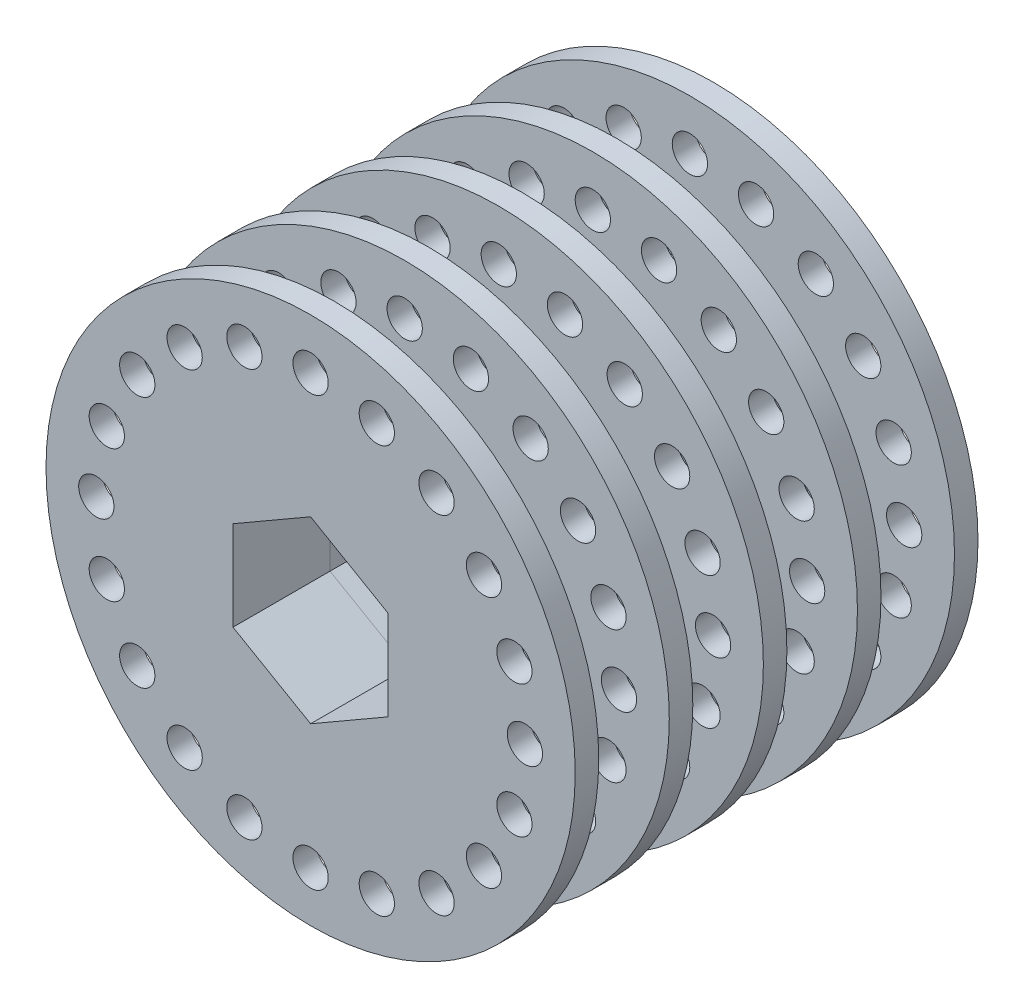
SolidWorks part; units mm, degrees
ref_plane "Front Plane" through (0, 0, 0) normal (0, 0, 1) x (1, 0, 0)
ref_plane "Top Plane" through (0, 0, 0) normal (0, 1, 0) x (1, 0, 0)
ref_plane "Right Plane" through (0, 0, 0) normal (1, 0, 0) x (0, 0, -1)
sketch "Sketch1" plane through (0, 0, 0) normal (0, 0, 1) x (1, 0, 0)
  circle A0 centre (0, 0) radius 10.16
  circle A1 centre (0, 0) radius 22.5
  circle A2 centre (0, 18.2218) radius 1.5
  circle A3 centre (5.6309, 17.33) radius 1.5
  circle A4 centre (10.7105, 14.7418) radius 1.5
  circle A5 centre (14.7418, 10.7105) radius 1.5
  circle A6 centre (17.33, 5.6309) radius 1.5
  circle A7 centre (18.2218, 0) radius 1.5
  circle A8 centre (17.33, -5.6309) radius 1.5
  circle A9 centre (14.7418, -10.7105) radius 1.5
  circle A10 centre (10.7105, -14.7418) radius 1.5
  circle A11 centre (5.6309, -17.33) radius 1.5
  circle A12 centre (0, -18.2218) radius 1.5
  circle A13 centre (-5.6309, -17.33) radius 1.5
  circle A14 centre (-10.7105, -14.7418) radius 1.5
  circle A15 centre (-14.7418, -10.7105) radius 1.5
  circle A16 centre (-17.33, -5.6309) radius 1.5
  circle A17 centre (-18.2218, 0) radius 1.5
  circle A18 centre (-17.33, 5.6309) radius 1.5
  circle A19 centre (-14.7418, 10.7105) radius 1.5
  circle A20 centre (-10.7105, 14.7418) radius 1.5
  circle A21 centre (-5.6309, 17.33) radius 1.5
  point P47 (0, 0)
  dimension "D1" = 20.32
  dimension "D2" = 45
  dimension "D3" = 3
  dimension "D4" = 20
extrude "Boss-Extrude1" add sketch "Sketch1" along normal blind 2 contours A0 | A1 A21 A20 A19 A18 A17 A16 A15 A14 A13 A12 A11 A10 A9 A8 A7 A6 A5 A4 A3 A2 A0 region at (0, 0, 0) region at (-21.8636, 0, 0)
extrude "Boss-Extrude2" add sketch "Sketch1<3>" against normal blind 6.25 contours A0 region at (0, 0, 0)
sketch "Sketch1<3>" plane through (0, 0, 0) normal (0, 0, 1) x (1, 0, 0) same geometry as "Sketch1"
pattern_linear "LPattern2" count 4 spacing 8 along (0, 0, -1) of "Boss-Extrude2", "Boss-Extrude1"
sketch "Sketch2" plane through (0, 0, -30.25) normal (0, 0, -1) x (-1, 0, 0)
  circle A1 centre (0, 0) radius 10.16 construction
  circle A2 centre (0, 0) radius 22.5 construction
  circle A3 centre (0, 0) radius 10.16
  circle A4 centre (0, 0) radius 22.5
  circle A5 centre (10.7105, 14.7418) radius 1.5
  circle A6 centre (10.7105, 14.7418) radius 1.5
  circle A7 centre (14.7418, 10.7105) radius 1.5
  circle A8 centre (14.7418, 10.7105) radius 1.5
  circle A9 centre (17.33, 5.6309) radius 1.5
  circle A10 centre (17.33, 5.6309) radius 1.5
  circle A11 centre (18.2218, 0) radius 1.5
  circle A12 centre (18.2218, 0) radius 1.5
  circle A13 centre (17.33, -5.6309) radius 1.5
  circle A14 centre (17.33, -5.6309) radius 1.5
  circle A15 centre (14.7418, -10.7105) radius 1.5
  circle A16 centre (14.7418, -10.7105) radius 1.5
  circle A17 centre (10.7105, -14.7418) radius 1.5
  circle A18 centre (10.7105, -14.7418) radius 1.5
  circle A19 centre (5.6309, -17.33) radius 1.5
  circle A20 centre (5.6309, -17.33) radius 1.5
  circle A21 centre (0, -18.2218) radius 1.5
  circle A22 centre (0, -18.2218) radius 1.5
  circle A23 centre (-5.6309, -17.33) radius 1.5
  circle A24 centre (-5.6309, -17.33) radius 1.5
  circle A25 centre (-10.7105, -14.7418) radius 1.5
  circle A26 centre (-10.7105, -14.7418) radius 1.5
  circle A27 centre (-14.7418, -10.7105) radius 1.5
  circle A28 centre (-14.7418, -10.7105) radius 1.5
  circle A29 centre (-17.33, -5.6309) radius 1.5
  circle A30 centre (-17.33, -5.6309) radius 1.5
  circle A31 centre (-18.2218, 0) radius 1.5
  circle A32 centre (-18.2218, 0) radius 1.5
  circle A33 centre (-17.33, 5.6309) radius 1.5
  circle A34 centre (-17.33, 5.6309) radius 1.5
  circle A35 centre (-14.7418, 10.7105) radius 1.5
  circle A36 centre (-14.7418, 10.7105) radius 1.5
  circle A37 centre (-10.7105, 14.7418) radius 1.5
  circle A38 centre (-10.7105, 14.7418) radius 1.5
  circle A39 centre (-5.6309, 17.33) radius 1.5
  circle A40 centre (-5.6309, 17.33) radius 1.5
  circle A41 centre (0, 18.2218) radius 1.5
  circle A42 centre (0, 18.2218) radius 1.5
  circle A43 centre (0, 0) radius 10.16
  circle A44 centre (0, 0) radius 10.16
  circle A45 centre (5.6309, 17.33) radius 1.5
  circle A46 centre (5.6309, 17.33) radius 1.5
  circle M22 centre (0, 0) radius 10.16
  dimension "D1" = 0
  dimension "D2" = 0
  dimension "D3" = 0
  dimension "D4" = 0
  dimension "D5" = 0
  dimension "D6" = 0
  dimension "D7" = 0
  dimension "D8" = 0
  dimension "D9" = 0
  dimension "D10" = 0
  dimension "D11" = 0
  dimension "D12" = 0
  dimension "D13" = 0
  dimension "D14" = 0
  dimension "D15" = 0
  dimension "D16" = 0
  dimension "D17" = 0
  dimension "D18" = 0
  dimension "D19" = 0
  dimension "D20" = 0
  dimension "D21" = 0
extrude "Boss-Extrude3" add sketch "Sketch2" along normal blind 2 contours A4 A46 A42 A40 A38 A36 A34 A32 A30 A28 A26 A24 A22 A20 A18 A16 A14 A12 A10 A8 A6 M22 | M22 region at (0, 0, -30.25) region at (21.8636, 0, -30.25)
sketch "Sketch3" plane through (0, 0, -32.25) normal (0, 0, -1) x (-1, 0, 0)
  line L1 (0, 7.621) -> (-6.6, 3.8105)
  line L2 (-6.6, 3.8105) -> (-6.6, -3.8105)
  line L3 (-6.6, -3.8105) -> (0, -7.621)
  line L4 (0, -7.621) -> (6.6, -3.8105)
  line L5 (6.6, -3.8105) -> (6.6, 3.8105)
  line L6 (6.6, 3.8105) -> (0, 7.621)
  circle A0 centre (0, 0) radius 6.6 construction
  circle A2 centre (0, 0) radius 19.05
  dimension "D2" = 38.1
extrude "Cut-Extrude1" cut sketch "Sketch3" against normal through all contours L5 L6 L1 L2 L3 L4 region at (0, 0, -32.25)
ref_plane "Plane1" through (0, 0, -3) normal (0, 0, -1) x (-1, 0, 0)
ref_plane "Plane2" through (0, 0, -11) normal (0, 0, -1) x (-1, 0, 0)
